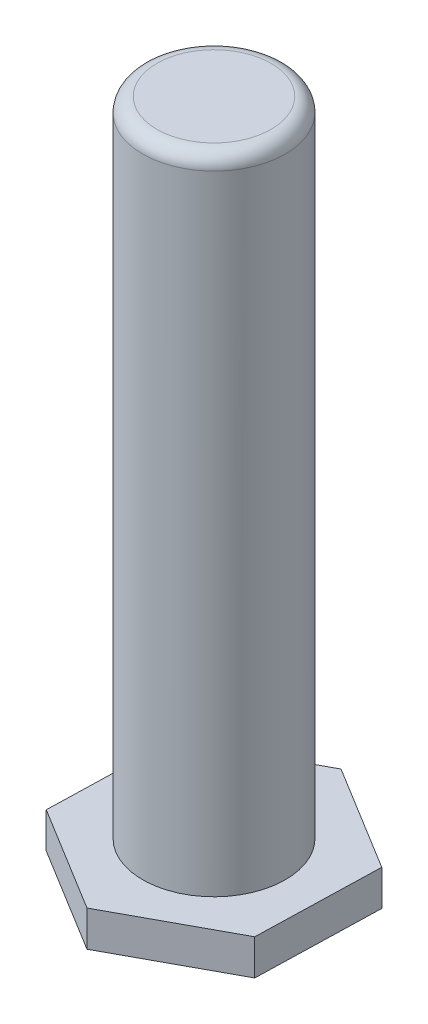
SolidWorks part; units mm, degrees
ref_plane "Plan de face" through (0, 0, 0) normal (0, 0, 1) x (1, 0, 0)
ref_plane "Plan de dessus" through (0, 0, 0) normal (0, 1, 0) x (1, 0, 0)
ref_plane "Plan de droite" through (0, 0, 0) normal (1, 0, 0) x (0, 0, -1)
sketch "Esquisse1" plane through (0, 0, 0) normal (0, 1, 0) x (1, 0, 0)
  line L1 (-14.768, 9.0622) -> (-15.232, -8.2584)
  line L2 (-15.232, -8.2584) -> (-0.4641, -17.3205)
  line L3 (-0.4641, -17.3205) -> (14.768, -9.0622)
  line L4 (14.768, -9.0622) -> (15.232, 8.2584)
  line L5 (15.232, 8.2584) -> (0.4641, 17.3205)
  line L6 (0.4641, 17.3205) -> (-14.768, 9.0622)
  circle A0 centre (0, 0) radius 15.0054 construction
  dimension "D1" = 30
extrude "Boss.-Extru.1" add sketch "Esquisse1" along normal blind 5
sketch "Esquisse2" plane through (0, 5, 0) normal (0, 1, 0) x (1, 0, 0)
  circle A0 centre (0, 0) radius 10
  dimension "D1" = 20
extrude "Boss.-Extru.2" add sketch "Esquisse2" along normal blind 90
cosmetic thread "Représentation de filetage1" parameters "D1"=10, "D2"=14.344
fillet "Congé1" radius 2 1 edges at (0, 95, 10)
